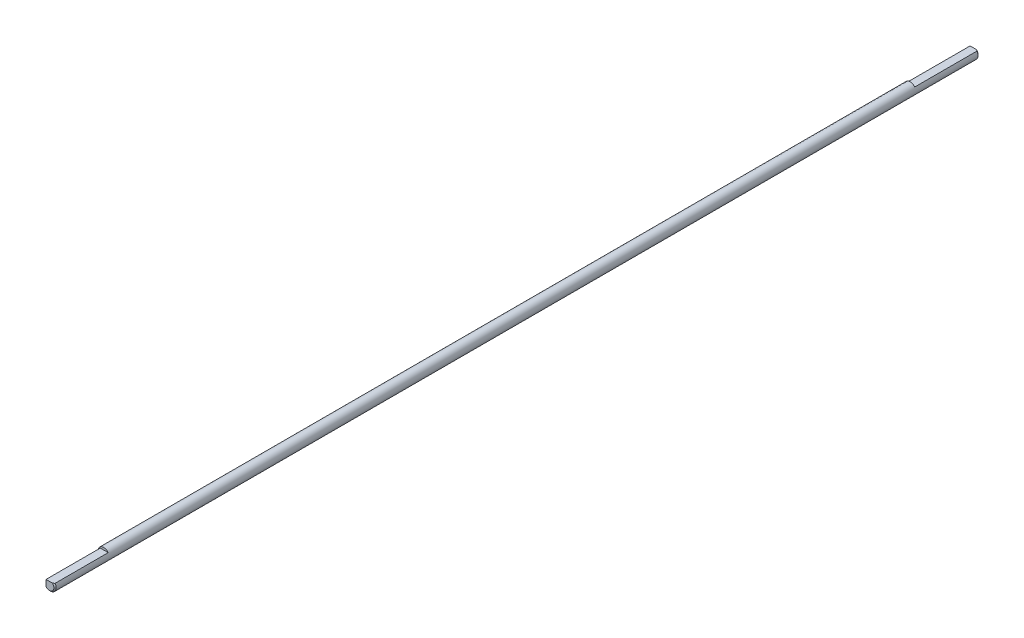
SolidWorks part; units mm, degrees
material "AISI 1020"
ref_plane "Спереди" through (0, 0, 0) normal (0, 0, 1) x (1, 0, 0)
ref_plane "Сверху" through (0, 0, 0) normal (0, 1, 0) x (1, 0, 0)
ref_plane "Справа" through (0, 0, 0) normal (1, 0, 0) x (0, 0, -1)
sketch "Эскиз1" plane through (0, 0, 0) normal (0, 0, 1) x (1, 0, 0)
  circle A0 centre (0, 0) radius 2.5
  dimension "D1" = 5
extrude "Body" add sketch "Эскиз1" along normal blind 408.5
chamfer "ChamferEdges" distance 0.5 angle 45 2 edges at (2.5, 0, 408.5) (2.5, 0, 0)
sketch "Sketch2" plane through (0, 0, 0) normal (1, 0, 0) x (0, 0, -1)
  line L0 (-408.5, 2) -> (-408.5, -2) construction
  line L1 (-28, 4.0099) -> (0.6305, 4.0099)
  line L2 (-28, 4.0099) -> (-28, 1.5)
  line L3 (-28, 1.5) -> (0.6305, 1.5)
  line L4 (0.6305, 4.0099) -> (0.6305, 1.5)
  line L6 (-408, -2.5) -> (-0.5, -2.5) construction
  line L11 (-384.5, 3.4421) -> (-384.5, 1.5)
  line L13 (-412.5, 3.4421) -> (-384.5, 3.4421)
  line L14 (-412.5, 3.4421) -> (-412.5, 1.5)
  line L15 (-412.5, 1.5) -> (-384.5, 1.5)
  dimension "D1" = 28
  dimension "D2" = 4
  dimension "D4" = 24
extrude "FirstSlots" cut sketch "Sketch2" against normal through all both and the other way through all
pattern_circular "AnotherSlots" count 2 every 90 about axis through (0, 0, 408.5) along (0, 0, 1) of "FirstSlots"
